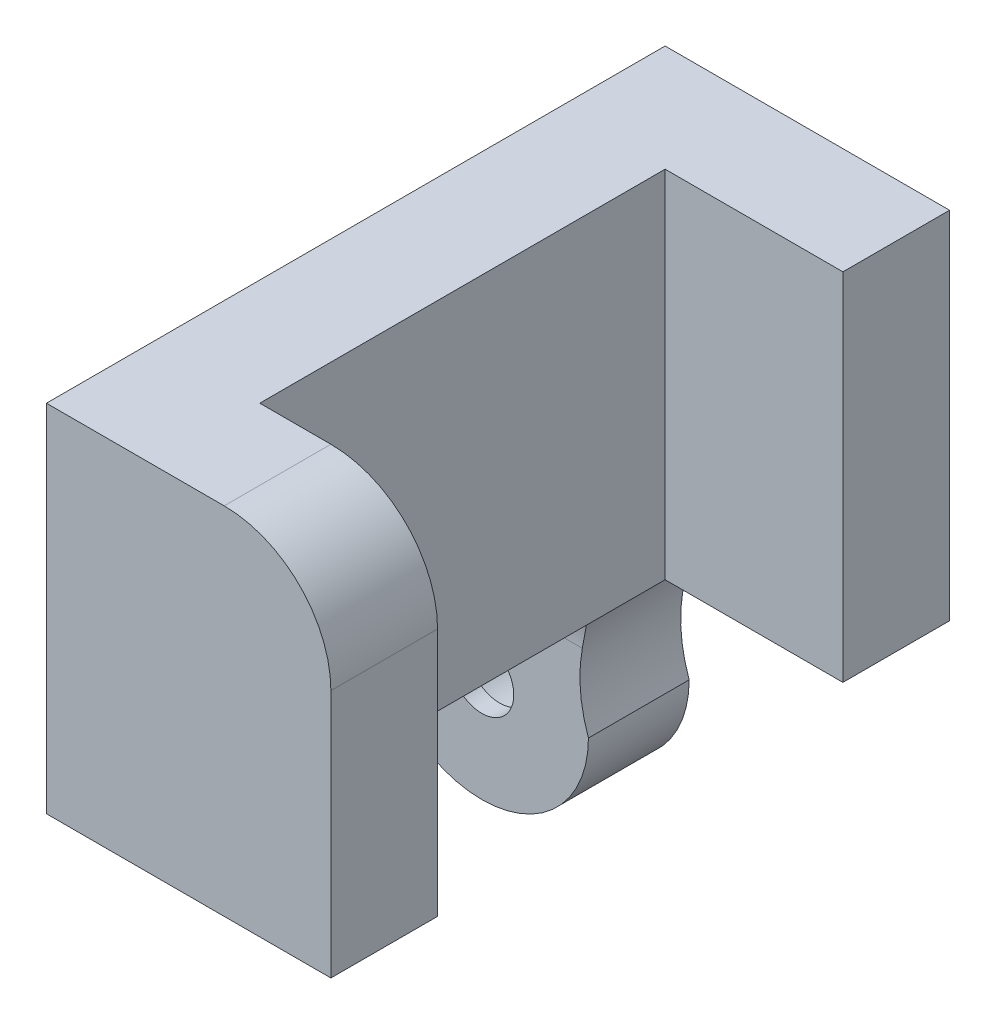
SolidWorks part; units mm, degrees
other "Marca1"
sketch "Croquis5" plane through (-41.9891, 32, -45) normal (-0.9335, 0.1055, -0.3427) x (-0.3417, 0.0277, 0.9394)
ref_plane "Alzado" through (0, 0, 0) normal (0, 0, 1) x (1, 0, 0)
ref_plane "Planta" through (0, 0, 0) normal (0, 1, 0) x (1, 0, 0)
ref_plane "Vista lateral" through (0, 0, 0) normal (1, 0, 0) x (0, 0, -1)
sketch "Croquis1" plane through (0, 0, 0) normal (1, 0, 0) x (0, 0, -1)
  line L0 (0, 42) -> (0, -48) construction
  line L2 (-42, 32) -> (-27, 32)
  line L3 (-42, 32) -> (-42, -18)
  line L4 (-42, -18) -> (-27, -18)
  line L5 (-27, 32) -> (-27, -18)
  line L6 (30, 32) -> (45, 32)
  line L7 (30, 32) -> (30, -18)
  line L8 (30, -18) -> (45, -18)
  line L9 (45, 32) -> (45, -18)
  point P11 (0, 0)
  point P12 (0, 0)
  dimension "D1" = 15
  dimension "D2" = 15
  dimension "D3" = 57
  dimension "D4" = 30
  dimension "D5" = 50
  dimension "D6" = 10
extrude "Saliente-Extruir1" add sketch "Croquis1" along normal blind 25
sketch "Croquis2" plane through (0, 0, 0) normal (-1, 0, 0) x (0, 0, 1)
  line L1 (-45, 32) -> (42, 32)
  line L2 (-45, 32) -> (-45, -18)
  line L3 (-45, -18) -> (42, -18)
  line L4 (42, 32) -> (42, -18)
extrude "Saliente-Extruir2" add sketch "Croquis2" along normal blind 15
sketch "Croquis3" plane through (0, 0, -30.8334) normal (0, 0, -1) x (-1, 0, 0)
  line L0 (15, -18) -> (-25, -18) construction
  line L1 (15, 32) -> (15, -18) construction
  line L2 (0, -18) -> (15, -18)
  line L3 (15, -18) -> (15, 7)
  arc A0 (11.6148, -43.4971) -> (41.6148, -43.4971) centre (26.6148, -43.4971) ccw
  arc A1 (11.6148, -43.4971) -> (0, -18) centre (-7.1824, -36.6658) ccw
  arc A2 (41.6148, -43.4971) -> (15, 7) centre (-8.0109, -37.3903) ccw
  point P1 (0, 0)
  dimension "D1" = 30
  dimension "D3" = 20
  dimension "D4" = 25
  dimension "D5" = 50
  dimension "D2" = 25
extrude "Saliente-Extruir3" add sketch "Croquis3" along normal up to surface (14.1666 mm away) up to face at (5, 7, -45)
fillet "Redondeo1" radius 15 3 edges at (-7.5, -18, -30.8334) (-15, -5.5, -30.8334) (-15, 7, -37.9167)
sketch "Croquis4" plane through (0, 0, -45) normal (0, 0, -1) x (-1, 0, 0)
  arc A4 (20.5517, -39.0825) -> (32.678, -39.0825) centre (26.6148, -43.4971) ccw
  arc A5 (29.6148, -25.4971) -> (23.6148, -25.4971) centre (26.6148, -25.4971) ccw
  arc A6 (20.5517, -39.0825) -> (23.6148, -25.4971) centre (-75.2311, -10.3481) ccw
  arc A7 (32.678, -39.0825) -> (29.6148, -25.4971) centre (128.4607, -10.3481) cw
  dimension "D8" = 15
  dimension "D9" = 6
  dimension "D10" = 18
  dimension "D11" = 100
  dimension "D12" = 100
extrude "Cortar-Extruir1" cut sketch "Croquis4" against normal blind 11.66
sketch "Croquis6" plane through (0, 0, -33.34) normal (0, 0, -1) x (-1, 0, 0)
  circle A0 centre (26.6148, -43.4971) radius 4.5
  circle A1 centre (26.6148, -35.9971) radius 1
  circle A2 centre (26.6148, -30.9971) radius 1
  dimension "D1" = 9
  dimension "D2" = 2
  dimension "D3" = 2
  dimension "D4" = 7.5
  dimension "D5" = 5
extrude "Cortar-Extruir2" cut sketch "Croquis6" against normal through all
fillet "Redondeo2" radius 15 1 edges at (25, 32, 34.5)
